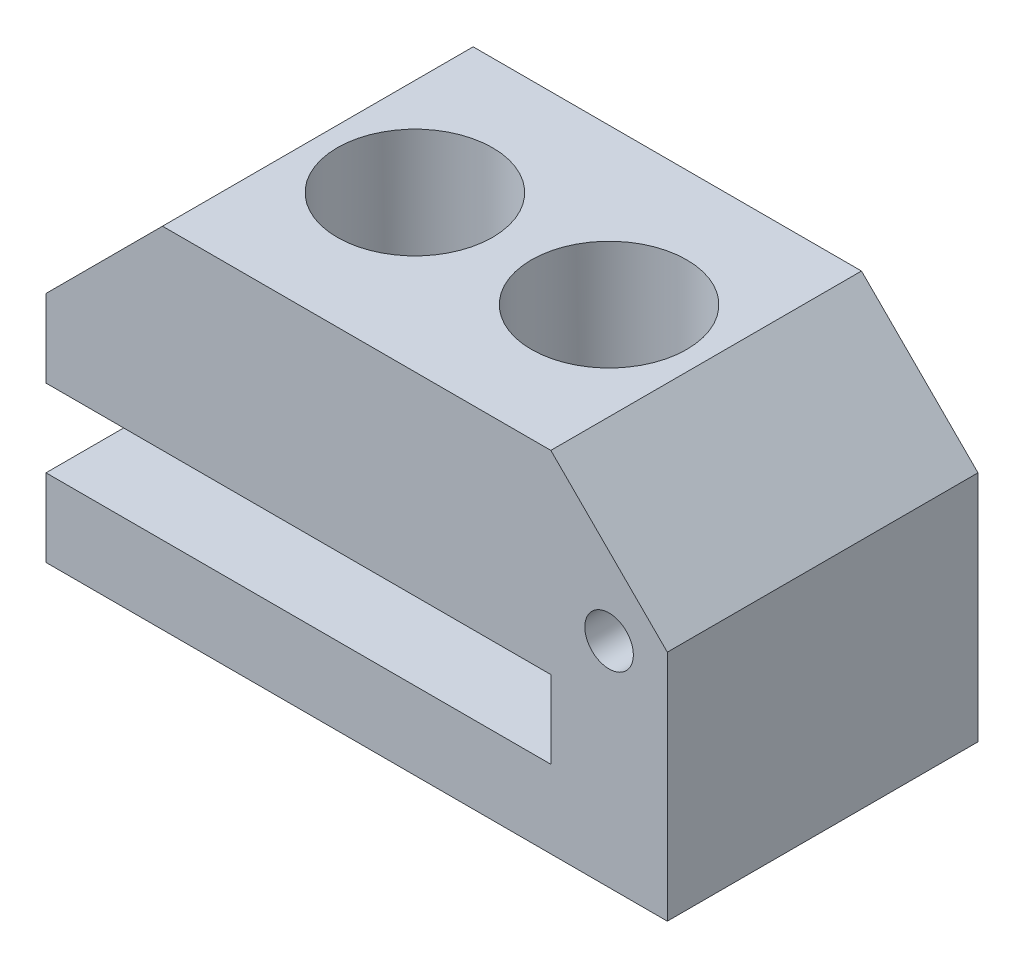
SolidWorks part; units mm, degrees
material "Brass"
ref_plane "Front Plane" through (0, 0, 0) normal (0, 0, 1) x (1, 0, 0)
ref_plane "Top Plane" through (0, 0, 0) normal (0, 1, 0) x (1, 0, 0)
ref_plane "Right Plane" through (0, 0, 0) normal (1, 0, 0) x (0, 0, -1)
sketch "Sketch1" plane through (0, 0, 0) normal (0, 0, 1) x (1, 0, 0)
  line L0 (0, 0) -> (32, 0)
  line L1 (32, 0) -> (32, 12)
  line L2 (32, 12) -> (26, 18)
  line L3 (26, 18) -> (6, 18)
  line L4 (6, 18) -> (0, 12)
  line L5 (0, 12) -> (0, 0)
  dimension "D1" = 32
  dimension "D2" = 12
  dimension "D3" = 6
  dimension "D4" = 6
  dimension "D5" = 20
  dimension "D6" = 6
  dimension "D7" = 6
extrude "Boss-Extrude1" add sketch "Sketch1" along normal blind 16
sketch "Sketch2" plane through (0, 0, 0) normal (0, 1, 0) x (1, 0, 0)
  circle A0 centre (11, -8) radius 4
  circle A1 centre (21, -8) radius 4
  dimension "D3" = 8
  dimension "D6" = 8
  dimension "D1" = 11
  dimension "D2" = 8
  dimension "D4" = 21
  dimension "D5" = 8
extrude "Cut-Extrude1" cut sketch "Sketch2" against normal mid plane 80
sketch "Sketch3" plane through (0, 0, 0) normal (0, 0, 1) x (1, 0, 0)
  line L0 (0, 4) -> (26, 4)
  line L1 (0, 12) -> (0, 0) construction
  line L2 (26, 4) -> (26, 8)
  line L3 (26, 8) -> (0, 8)
  line L4 (0, 8) -> (0, 4)
  dimension "D1" = 26
  dimension "D2" = 4
  dimension "D3" = 4
extrude "Cut-Extrude2" cut sketch "Sketch3" against normal mid plane 80
sketch "Sketch4" plane through (0, 0, 0) normal (0, 0, 1) x (1, 0, 0)
  circle A0 centre (29, 11) radius 1.25
  dimension "D3" = 2.5
  dimension "D1" = 29
  dimension "D2" = 11
extrude "Cut-Extrude3" cut sketch "Sketch4" against normal mid plane 80
